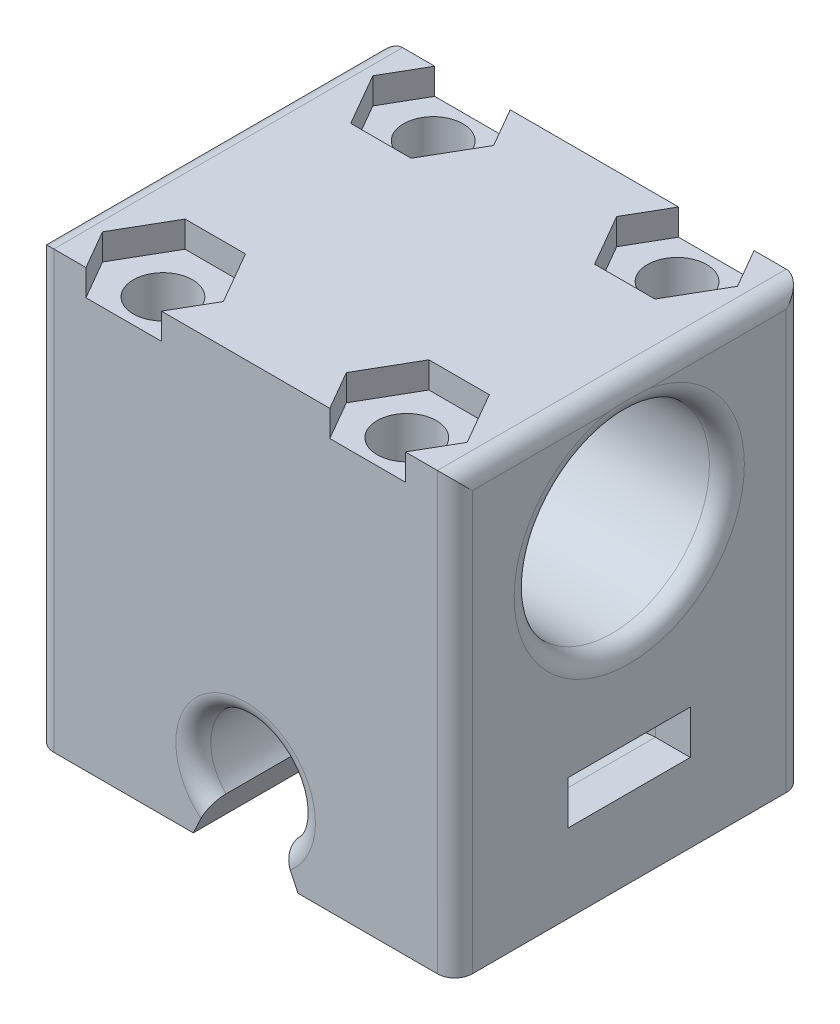
SolidWorks part; units mm, degrees
ref_plane "Alzado" through (0, 0, 0) normal (0, 0, 1) x (1, 0, 0)
ref_plane "Planta" through (0, 0, 0) normal (0, 1, 0) x (1, 0, 0)
ref_plane "Vista lateral" through (0, 0, 0) normal (1, 0, 0) x (0, 0, -1)
sketch "Croquis1" plane through (0, 0, 0) normal (0, -1, 0) x (1, 0, 0)
  line L1 (26.4565, 24.3192) -> (50.4565, 24.3192)
  line L2 (26.4565, 24.3192) -> (26.4565, 4.3192)
  line L3 (26.4565, 4.3192) -> (50.4565, 4.3192)
  line L4 (50.4565, 24.3192) -> (50.4565, 4.3192)
  dimension "D1" = 24
  dimension "D2" = 20
extrude "Saliente-Extruir1" add sketch "Croquis1" against normal blind 25 separate body
sketch "Croquis2" plane through (0, 0, 24.3192) normal (0, 0, 1) x (1, 0, 0)
  line L0 (35.4565, 0) -> (36.3351, 1.8787)
  line L2 (40.5778, 1.8787) -> (41.4565, 0)
  line L3 (41.4565, 0) -> (35.4565, 0)
  line L5 (50.4565, 25) -> (50.4565, 0) construction
  line L6 (50.4565, 0) -> (26.4565, 0) construction
  arc A0 (40.5778, 1.8787) -> (36.3351, 1.8787) centre (38.4565, 4) ccw
  dimension "D1" = 3
  dimension "D4" = 1.0228
  dimension "D5" = 9
  dimension "D2" = 6
  dimension "D3" = 2.074
  dimension "D6" = 25
extrude "Cortar-Extruir1" cut sketch "Croquis2" against normal through all
sketch "Croquis3" plane through (50.4565, 0, 0) normal (1, 0, 0) x (0, 0, -1)
  line L0 (-4.3192, 0) -> (-24.3192, 0) construction
  line L1 (-4.3192, 25) -> (-4.3192, 0) construction
  circle A0 centre (-14.3192, 17.5) radius 5.6
  dimension "D1" = 11.2
  dimension "D2" = 10
  dimension "D3" = 17.5
extrude "Cortar-Extruir2" cut sketch "Croquis3" against normal through all
sketch "Croquis4" plane through (0, 0, 0) normal (0, -1, 0) x (1, 0, 0)
  line L0 (38.4565, 34.8249) -> (38.4565, -1.1794) construction
  line L2 (95.5089, 14.3192) -> (58.9949, 14.3192) construction
  line L4 (26.4565, 24.3192) -> (26.4565, 4.3192) construction
  line L6 (35.4565, 4.3192) -> (35.4565, 24.3192) construction
  circle A0 centre (31.4643, 22.0692) radius 1.7
  circle A1 centre (45.4486, 22.0692) radius 1.7
  circle A2 centre (45.4486, 6.5692) radius 1.7
  circle A3 centre (31.4643, 6.5692) radius 1.7
  dimension "D1" = 12
  dimension "D3" = 3.4
  dimension "D2" = 10
  dimension "D4" = 9.9921
  dimension "D5" = 2.25
extrude "Cortar-Extruir3" cut sketch "Croquis4" against normal through all
sketch "Croquis6" plane through (0, 25, 0) normal (0, 1, 0) x (1, 0, 0)
  line L0 (38.4565, 2.8712) -> (38.4565, -28.7183) construction
  line L1 (42.1324, -4.3131) -> (50.4565, -4.3192)
  line L2 (92.8267, -14.3192) -> (57.3757, -14.3192) construction
  line L5 (50.4565, -4.3192) -> (50.4565, -9.4129)
  line L6 (28.6357, -9.4129) -> (26.4565, -9.4129)
  line L7 (26.4565, -4.3192) -> (26.4565, -9.4129)
  line L8 (48.2772, -9.4129) -> (50.4565, -9.4129)
  line L9 (34.7806, -4.3131) -> (26.4565, -4.3192)
  line L10 (48.2772, -19.2255) -> (50.4565, -19.2255)
  line L12 (50.4565, -24.3192) -> (50.4565, -19.2255)
  line L13 (42.1324, -24.3253) -> (50.4565, -24.3192)
  line L14 (34.7806, -24.3253) -> (26.4565, -24.3192)
  line L15 (26.4565, -24.3192) -> (26.4565, -19.2255)
  line L16 (28.6357, -19.2255) -> (26.4565, -19.2255)
  arc A0 (28.6357, -9.4129) -> (34.7806, -4.3131) centre (31.4643, -6.5692) ccw
  arc A1 (48.2772, -19.2255) -> (42.1324, -24.3253) centre (45.4486, -22.0692) ccw
  arc A2 (28.6357, -19.2255) -> (34.7806, -24.3253) centre (31.4643, -22.0692) cw
  arc A4 (48.2772, -9.4129) -> (42.1324, -4.3131) centre (45.4486, -6.5692) cw
  circle A8 centre (31.4643, -22.0692) radius 1.7 construction
  dimension "D1" = 12
  dimension "D3" = 4.0109
  dimension "D5" = 18.9921
  dimension "D2" = 10
  dimension "D4" = 3.3162
  dimension "D6" = 17.75
  dimension "D7" = 16.8128
extrude "Cortar-Extruir4" [suppressed] cut sketch "Croquis6" against normal blind 2
sketch "Croquis7" [suppressed] plane through (0, 23, 0) normal (0, 1, 0) x (1, 0, 0)
  line L0 (26.4565, -4.3192) -> (28.1572, -4.3192)
  line L1 (26.4565, -4.3192) -> (26.4565, -6.4053)
  line L2 (50.4565, -6.4053) -> (49.4452, -6.4053)
  line L3 (26.4565, -6.4053) -> (27.4677, -6.4053)
  line L4 (50.4565, -4.3192) -> (50.4565, -6.4053)
  line L5 (38.4565, 2.8236) -> (38.4565, -30.8763) construction
  line L6 (93.1844, -14.3192) -> (59.0283, -14.3192) construction
  line L7 (50.4565, -4.3192) -> (48.7558, -4.3192)
  line L8 (50.4565, -24.3192) -> (48.7558, -24.3192)
  line L9 (50.4565, -24.3192) -> (50.4565, -22.2331)
  line L10 (50.4565, -22.2331) -> (49.4452, -22.2331)
  line L11 (26.4565, -22.2331) -> (27.4677, -22.2331)
  line L12 (26.4565, -24.3192) -> (26.4565, -22.2331)
  line L13 (26.4565, -24.3192) -> (28.1572, -24.3192)
  line L16 (26.4565, -4.3192) -> (26.4565, -9.4129) construction
  arc A0 (28.1572, -4.3192) -> (27.4677, -6.4053) centre (31.4643, -6.5692) ccw
  arc A1 (48.7558, -4.3192) -> (49.4452, -6.4053) centre (45.4486, -6.5692) cw
  arc A2 (48.7558, -24.3192) -> (49.4452, -22.2331) centre (45.4486, -22.0692) ccw
  arc A3 (28.1572, -24.3192) -> (27.4677, -22.2331) centre (31.4643, -22.0692) cw
  dimension "D1" = 10
  dimension "D3" = 4
  dimension "D2" = 12
  dimension "D4" = 1.0112
  dimension "D5" = 1.7007
  dimension "D6" = 5.0079
extrude "Cortar-Extruir5" [suppressed] cut sketch "Croquis7" against normal blind 13
sketch "Croquis8" plane through (50.4565, 0, 0) normal (1, 0, 0) x (0, 0, -1)
  line L1 (-17.8192, 7) -> (-10.8192, 7)
  line L2 (-17.8192, 7) -> (-17.8192, 4.5)
  line L3 (-17.8192, 4.5) -> (-10.8192, 4.5)
  line L4 (-10.8192, 7) -> (-10.8192, 4.5)
  line L5 (-4.3192, 0) -> (-24.3192, 0) construction
  dimension "D1" = 7
  dimension "D2" = 2.5
  dimension "D3" = 6.5
  dimension "D4" = 4.5
ref_plane "Plano1" through (0, 0, 10.8192) normal (0, 0, -1) x (-1, 0, 0)
sketch "Croquis9" plane through (0, 0, 10.8192) normal (0, 0, -1) x (-1, 0, 0)
  line L0 (-41.4565, 0) -> (-50.4565, 0) construction
  line L1 (-48.4565, 7) -> (-50.4565, 7)
  line L2 (-43.4565, 2) -> (-43.4565, 0)
  line L3 (-50.4565, 25) -> (-50.4565, 0) construction
  arc A0 (-43.4565, 2) -> (-48.4565, 7) centre (-48.4565, 2) ccw
  dimension "D1" = 5
  dimension "D2" = 2
  dimension "D3" = 2
sweep "Cortar-Barrer2" cut profiles "Croquis8" path "Croquis9"
sketch "Croquis10" plane through (0, 0, 0) normal (0, -1, 0) x (1, 0, 0)
  line L1 (45.9565, 17.8192) -> (46.4565, 17.8192)
  line L2 (45.9565, 17.8192) -> (45.9565, 10.8192)
  line L3 (45.9565, 10.8192) -> (46.4565, 10.8192)
  line L4 (46.4565, 17.8192) -> (46.4565, 10.8192)
  dimension "D1" = 0.5
  dimension "D2" = 7
extrude "Cortar-Extruir6" [suppressed] cut sketch "Croquis10" against normal up to surface (4.5 mm away)
ref_plane "Plano2" through (38.4565, 0, 0) normal (1, 0, 0) x (0, 0, -1)
mirror "Simetría1" about plane through (38.4565, 0, 0) normal (1, 0, 0) of "Cortar-Extruir6", "Cortar-Barrer2"
sketch "Croquis11" plane through (0, 25, 0) normal (0, 1, 0) x (1, 0, 0)
  line L0 (50.4565, -24.3192) -> (26.4565, -24.3192) construction
  line L1 (47.1806, -19.0692) -> (43.7165, -19.0692)
  line L2 (43.7165, -19.0692) -> (41.9845, -22.0692)
  line L3 (41.9845, -22.0692) -> (43.7165, -25.0692)
  line L4 (43.7165, -25.0692) -> (47.1806, -25.0692)
  line L5 (47.1806, -25.0692) -> (48.9127, -22.0692)
  line L6 (48.9127, -22.0692) -> (47.1806, -19.0692)
  line L7 (26.4565, -4.3192) -> (50.4565, -4.3192) construction
  line L8 (34.9284, -22.0692) -> (33.1964, -19.0692)
  line L9 (33.1964, -19.0692) -> (29.7323, -19.0692)
  line L10 (29.7323, -19.0692) -> (28.0002, -22.0692)
  line L11 (28.0002, -22.0692) -> (29.7323, -25.0692)
  line L12 (29.7323, -25.0692) -> (33.1964, -25.0692)
  line L13 (33.1964, -25.0692) -> (34.9284, -22.0692)
  line L14 (34.9284, -6.5692) -> (33.1964, -3.5692)
  line L15 (33.1964, -3.5692) -> (29.7323, -3.5692)
  line L16 (29.7323, -3.5692) -> (28.0002, -6.5692)
  line L17 (28.0002, -6.5692) -> (29.7323, -9.5692)
  line L18 (29.7323, -9.5692) -> (33.1964, -9.5692)
  line L19 (33.1964, -9.5692) -> (34.9284, -6.5692)
  line L20 (47.1806, -9.5692) -> (48.9127, -6.5692)
  line L21 (48.9127, -6.5692) -> (47.1806, -3.5692)
  line L22 (47.1806, -3.5692) -> (43.7165, -3.5692)
  line L23 (43.7165, -3.5692) -> (41.9845, -6.5692)
  line L24 (41.9845, -6.5692) -> (43.7165, -9.5692)
  line L25 (43.7165, -9.5692) -> (47.1806, -9.5692)
  circle A0 centre (45.4486, -22.0692) radius 3 construction
  circle A1 centre (31.4643, -22.0692) radius 3 construction
  circle A2 centre (31.4643, -6.5692) radius 3 construction
  circle A3 centre (45.4486, -6.5692) radius 3 construction
extrude "Cortar-Extruir7" cut sketch "Croquis11" against normal blind 1.5
fillet "Redondeo1" radius 1 10 edges at (26.4565, 12.5, 24.3192) (26.4565, 25, 14.3192) (26.4565, 12.5, 4.3192) (50.4565, 12.5, 4.3192) (50.4565, 12.5, 24.3192) (50.4565, 25, 14.3192) (26.4565, 17.5, 8.7192) (50.4565, 17.5, 8.7192) (38.4565, 7, 4.3192) (38.4565, 7, 24.3192)
